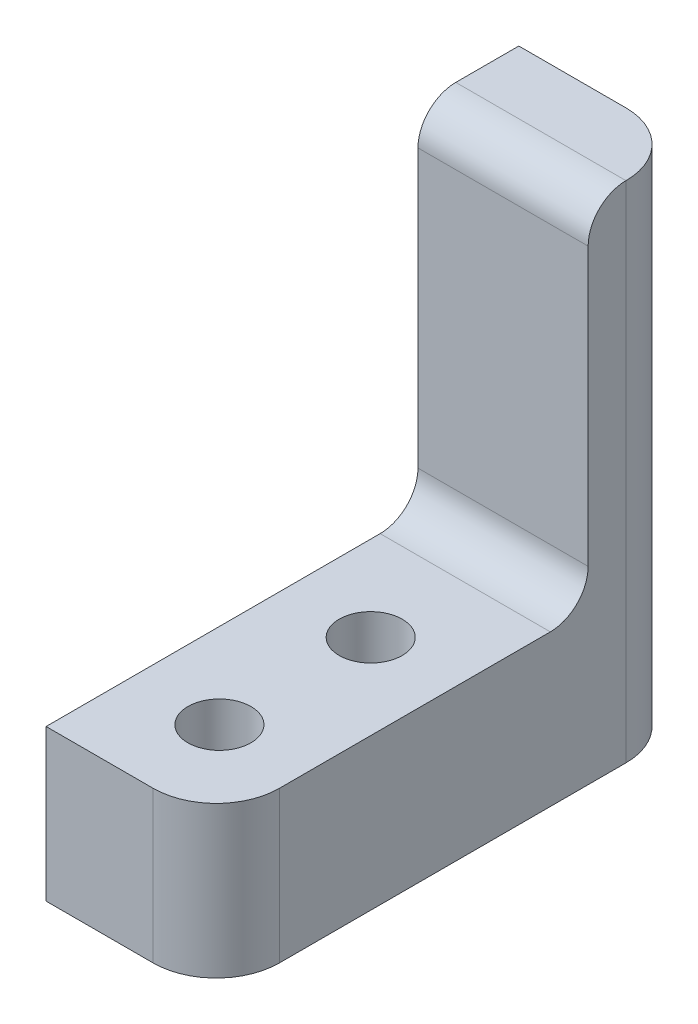
SolidWorks part; units mm, degrees
material "K110"
ref_plane "Front Plane" through (0, 0, 0) normal (0, 0, 1) x (1, 0, 0)
ref_plane "Top Plane" through (0, 0, 0) normal (0, 1, 0) x (1, 0, 0)
ref_plane "Right Plane" through (0, 0, 0) normal (1, 0, 0) x (0, 0, -1)
sketch "Sketch1" plane through (0, 0, 0) normal (0, 1, 0) x (1, 0, 0)
  line L1 (-20, -18.75) -> (20, -18.75)
  line L2 (-20, -18.75) -> (-20, 18.75)
  line L3 (-20, 18.75) -> (20, 18.75)
  line L4 (20, -18.75) -> (20, 18.75)
  line L5 (-20, -18.75) -> (20, 18.75) construction
  line L6 (-20, 18.75) -> (20, -18.75) construction
  point P0 (0, 0)
  dimension "D1" = 37.5
  dimension "D2" = 40
extrude "Boss-Extrude1" add sketch "Sketch1" against normal blind 40
sketch "Sketch2" plane through (20, 0, 0) normal (1, 0, 0) x (0, 0, -1)
  line L0 (18.75, -40) -> (18.75, 0) construction
  line L1 (-18.75, 0) -> (10.75, 0)
  line L2 (-18.75, 0) -> (-18.75, -28)
  line L3 (-18.75, -28) -> (10.75, -28)
  line L4 (10.75, 0) -> (10.75, -28)
  dimension "D1" = 8
  dimension "D2" = 28
extrude "Cut-Extrude1" cut sketch "Sketch2" against normal up to next
fillet "Fillet1" radius 3 2 edges at (0, 0, -10.75) (0, -28, -10.75)
hole_wizard "M6 Tapped Hole1" positions "Sketch12" profile "Sketch4" tap size "M6" standard "ISO" end condition through all
sketch "Sketch12" plane through (0, -40, 0) normal (0, -1, 0) x (-1, 0, 0)
  line L0 (-20, -18.75) -> (-20, 18.75) construction
  line L2 (20, -18.75) -> (-20, -18.75) construction
  point P0 (-13.25, -11.75)
  point P23 (-13.25, 0.25)
  dimension "D1" = 6.75
  dimension "D2" = 7
  dimension "D3" = 12
cosmetic thread "Hole Thread2" parameters "D2"=6
sketch "Sketch4" plane through (13.25, -40, 11.75) normal (1, 0, 0) x (0, 0, -1)
  line L0 (0, 0) -> (0, 40)
  line L1 (0, 40) -> (2.5, 40)
  line L2 (2.5, 40) -> (2.5, 0.525)
  line L3 (2.5, 0.525) -> (3.025, 0)
  line L5 (3.025, 0) -> (0, 0)
  line L6 (-2.5, 0.525) -> (-3.025, 0) construction
  line L11 (0, -6.35) -> (0, 107.95) construction
  dimension "Thru Tap Drill Dia." = 5
  dimension "Thru Tap Drill Depth" = 40
  dimension "Near C'Sink Dia." = 6.05
  dimension "Near C'Sink Angle" = 90
cosmetic thread "Hole Thread3" parameters "D2"=6
fillet "Fillet2" radius 5 4 edges at (20, -20, -18.75) (20, -34, 18.75) (-20, -34, 18.75) (-20, -20, -18.75)
sketch "Sketch7" plane through (0, 0, 0) normal (0, 1, 0) x (1, 0, 0)
  line L0 (-15, -18.75) -> (15, -18.75) construction
  line L1 (-6.5, -18.75) -> (6.5, -18.75)
  line L2 (-6.5, -18.75) -> (-6.5, 10.75)
  line L3 (-6.5, 10.75) -> (6.5, 10.75)
  line L4 (6.5, -18.75) -> (6.5, 10.75)
  line L6 (0, 7.75) -> (0, -18.75) construction
  line L7 (-20, 13.75) -> (20, 13.75) construction
  dimension "D1" = 3
  dimension "13" = 13
extrude "Cut-Extrude2" cut sketch "Sketch7" against normal up to next
sketch "Sketch8" plane through (0, 0, 0) normal (1, 0, 0) x (0, 0, -1)
  line L1 (-18.75, -40) -> (10.75, -40)
  line L2 (-18.75, -40) -> (-18.75, -3)
  line L3 (-18.75, -3) -> (10.75, -3)
  line L4 (10.75, -40) -> (10.75, -3)
extrude "Cut-Extrude3" cut sketch "Sketch8" against normal up to next
sketch "Sketch9" plane through (-20, 0, 0) normal (-1, 0, 0) x (0, 0, 1)
  line L0 (-10.75, -40) -> (-10.75, -3) construction
  line L1 (-18.75, -40) -> (-10.75, -40)
  line L2 (-18.75, -40) -> (-18.75, 4.9978)
  line L3 (-18.75, 4.9978) -> (-10.75, 4.9978)
  line L4 (-10.75, -40) -> (-10.75, 4.9978)
  line L5 (-23.7522, -7.0022) -> (-13.75, -7.0022) construction
  dimension "D1" = 12
extrude "Cut-Extrude4" cut sketch "Sketch9" against normal up to surface (26.5 mm away) up to face at (6.5, -32.3243, 1.5257)
